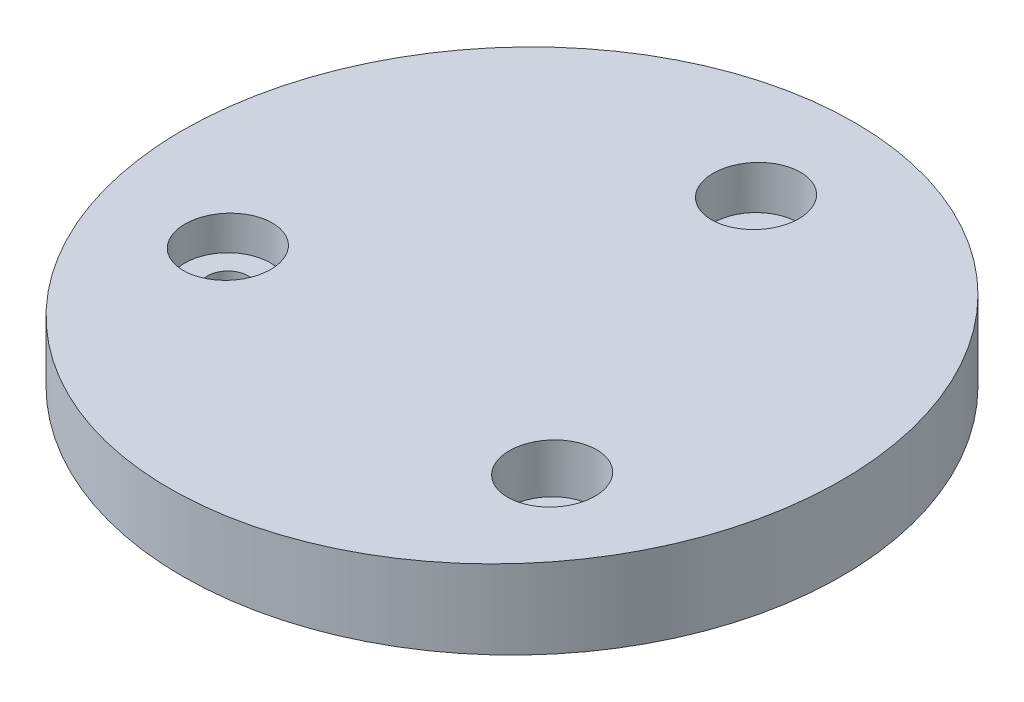
SolidWorks part; units mm, degrees
ref_plane "Front Plane" through (0, 0, 0) normal (0, 0, 1) x (1, 0, 0)
ref_plane "Top Plane" through (0, 0, 0) normal (0, 1, 0) x (1, 0, 0)
ref_plane "Right Plane" through (0, 0, 0) normal (1, 0, 0) x (0, 0, -1)
sketch "Sketch1" plane through (0, 0, 0) normal (0, 1, 0) x (1, 0, 0)
  circle A0 centre (0, 0) radius 25
  dimension "D1" = 50
extrude "Boss-Extrude1" add sketch "Sketch1" along normal blind 4.3
sketch "Sketch2" plane through (0, 0, 0) normal (0, 0, 1) x (1, 0, 0)
  line L0 (-25, 4.3) -> (25, 6.3)
  line L1 (25, 4.3) -> (-25, 4.3) construction
  line L2 (25, 6.3) -> (25, 4.3)
  line L3 (-25, 4.3) -> (25, 4.3)
  dimension "D1" = 2
extrude "Boss-Extrude2" add sketch "Sketch2" along normal up to surface and the other way up to surface up to face at (0, 4.3, 25) other way up to face at (0, 4.3, 25)
sketch "Sketch3" plane through (0, 0, 0) normal (0, 1, 0) x (1, 0, 0)
  line L0 (0, 0) -> (-20.9915, 0) construction
  line L1 (0, 0) -> (-26.3876, -10.9301) construction
  line L2 (0, 0) -> (-12.1543, 29.3431) construction
  circle A0 centre (0, 0) radius 16.5 construction
  circle A1 centre (-15.244, -6.3143) radius 1.55
  circle A2 centre (2.1537, 16.3588) radius 1.55
  circle A3 centre (13.0903, -10.0446) radius 1.55
  point P21 (0, 0)
  dimension "D3" = 33
  dimension "D4" = 3.1
  dimension "D5" = 3
  dimension "D1" = 22.5
  dimension "D2" = 90
extrude "Cut-Extrude1" cut sketch "Sketch3" along normal up to next
ref_plane "Plane1" through (0, 2, 0) normal (0, -1, 0) x (-1, 0, 0)
sketch "Sketch4" plane through (0, 2, 0) normal (0, -1, 0) x (-1, 0, 0)
  circle A0 centre (-2.1537, 16.3588) radius 3.25
  circle A1 centre (15.244, -6.3143) radius 3.25
  circle A2 centre (-13.0903, -10.0446) radius 3.25
  dimension "D1" = 6.5
extrude "Cut-Extrude2" cut sketch "Sketch4" against normal up to next
